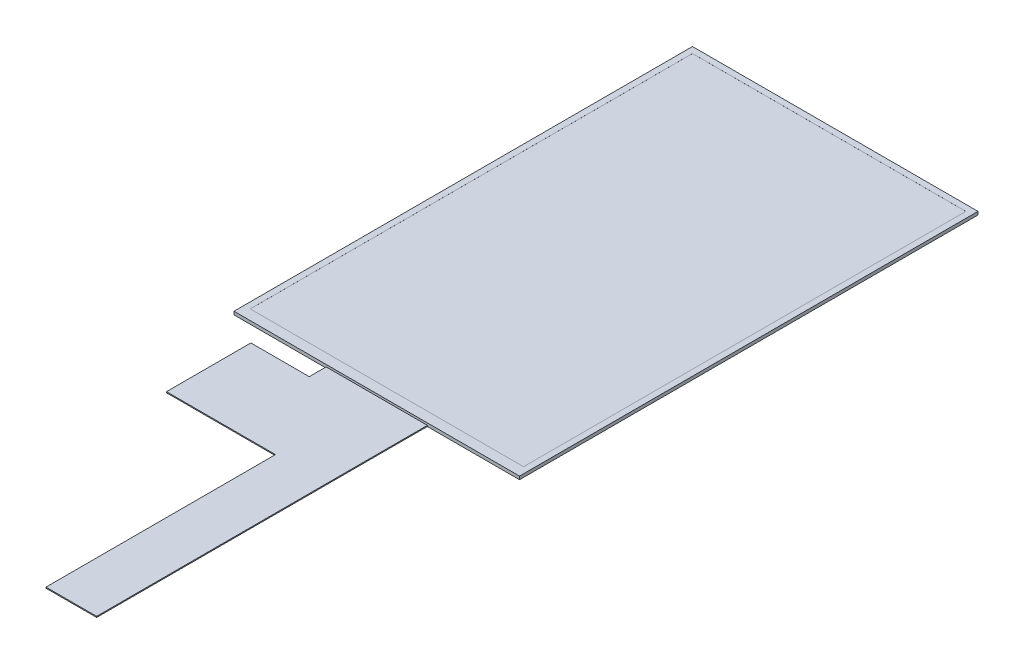
SolidWorks part; units mm, degrees
material "A-Glass Fiber"
ref_plane "Front Plane" through (0, 0, 0) normal (0, 0, 1) x (1, 0, 0)
ref_plane "Top Plane" through (0, 0, 0) normal (0, 1, 0) x (1, 0, 0)
ref_plane "Right Plane" through (0, 0, 0) normal (1, 0, 0) x (0, 0, -1)
sketch "Sketch1" plane through (0, 0, 0) normal (0, 1, 0) x (1, 0, 0)
  line L1 (-42.3, 0) -> (42.3, 0)
  line L2 (-42.3, 0) -> (-42.3, 135.85)
  line L3 (-42.3, 135.85) -> (42.3, 135.85)
  line L4 (42.3, 0) -> (42.3, 135.85)
  point P4 (0, 0)
  dimension "D1" = 84.6
  dimension "D2" = 135.85
extrude "Boss-Extrude1" add sketch "Sketch1" along normal blind 0.946
sketch "Sketch2" plane through (0, 0, 0) normal (0, 1, 0) x (1, 0, 0)
  line L0 (-15, 0) -> (-15, -5)
  line L1 (-42.3, 0) -> (42.3, 0) construction
  line L2 (-15, -5) -> (-32.3, -5)
  line L3 (-32.3, -5) -> (-32.3, -30)
  line L4 (-32.3, -30) -> (0, -30)
  line L5 (0, -30) -> (0, -98)
  line L6 (0, -98) -> (15, -98)
  line L7 (15, -98) -> (15, 0)
  line L8 (15, 0) -> (-15, 0)
  line L9 (-42.3, 135.85) -> (-42.3, 0) construction
  point P4 (0, 0)
  dimension "D1" = 5
  dimension "D2" = 15
  dimension "D3" = 98
  dimension "D4" = 25
  dimension "D5" = 10
extrude "Boss-Extrude2" add sketch "Sketch2" along normal blind 0.3 from offset 0.01
sketch "Sketch3" plane through (0, 0.946, 0) normal (0, 1, 0) x (1, 0, 0)
  line L0 (-42.3, 135.85) -> (-42.3, 0) construction
  line L1 (-40.5, 134.05) -> (40.5, 134.05)
  line L2 (-40.5, 134.05) -> (-40.5, 3)
  line L3 (-40.5, 3) -> (40.5, 3)
  line L4 (40.5, 134.05) -> (40.5, 3)
  line L5 (-40.5, 3) -> (-42.3, 3) construction
  line L6 (-40.5, 3) -> (-40.5, 0) construction
  line L7 (-42.3, 0) -> (42.3, 0) construction
  line L8 (42.3, 135.85) -> (-42.3, 135.85) construction
  line L9 (40.5, 134.05) -> (-40.5, 3) construction
  line L10 (-40.5, 134.05) -> (40.5, 3) construction
  point P4 (0, 3)
  dimension "D1" = 1.8
  dimension "D2" = 3
  dimension "D3" = 1.8
extrude "Cut-Extrude1" cut sketch "Sketch3" against normal blind 0.01
extrude "Cut-Extrude3" cut sketch "Sketch3<2>" along normal blind 0.01 from surface starting at face at (0, 0, -67.925)
sketch "Sketch3<2>" plane through (0, 0.946, 0) normal (0, 1, 0) x (1, 0, 0) same geometry as "Sketch3"
sketch "Sketch4" plane through (0, 0.01, 0) normal (0, -1, 0) x (1, 0, 0)
  line L0 (40.5, -134.05) -> (-40.5, -3) construction
  line L1 (-40.5, -134.05) -> (40.5, -3) construction
  line L2 (0, -99.026) -> (0, -38.024) construction
  line L3 (-30.501, -68.525) -> (30.501, -68.525) construction
  point P12 (0, -68.525)
  point P15 (0, -68.525)
